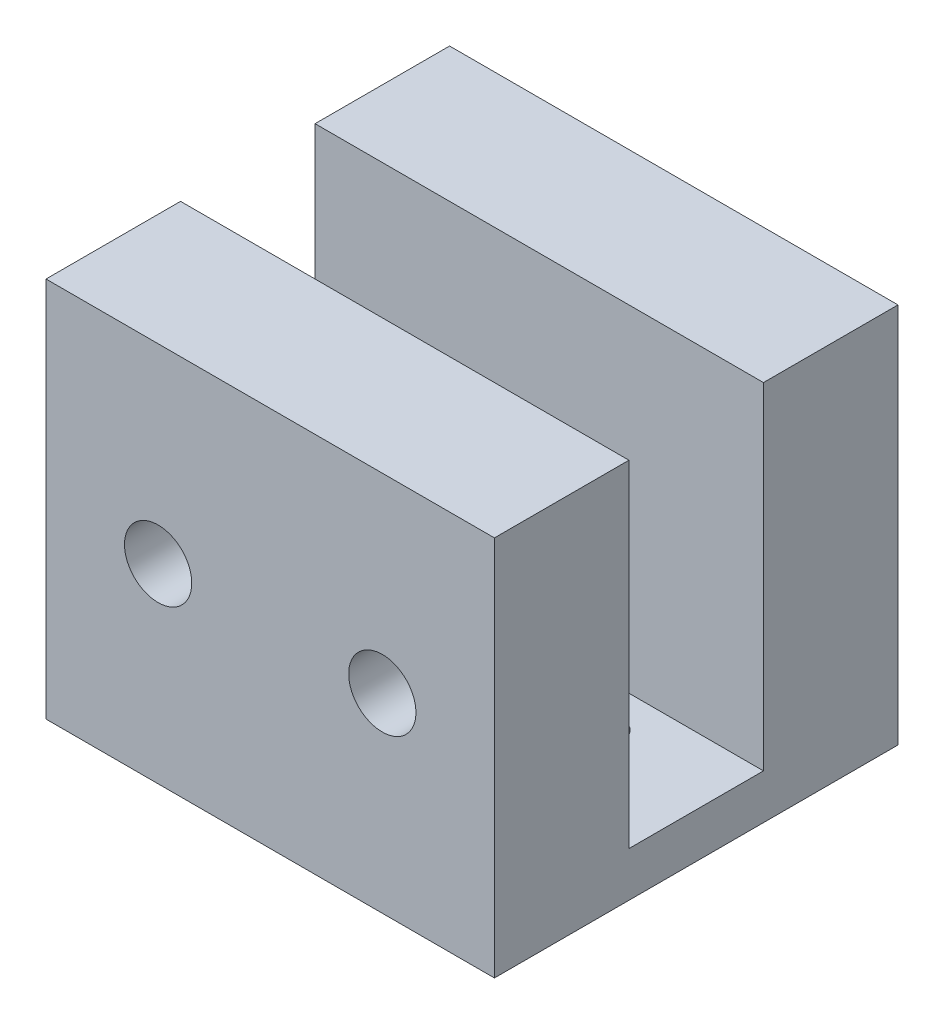
SolidWorks part; units mm, degrees
ref_plane "Plan de face" through (0, 0, 0) normal (0, 0, 1) x (1, 0, 0)
ref_plane "Plan de dessus" through (0, 0, 0) normal (0, 1, 0) x (1, 0, 0)
ref_plane "Plan de droite" through (0, 0, 0) normal (1, 0, 0) x (0, 0, -1)
sketch "Esquisse1" plane through (0, 0, 0) normal (0, 1, 0) x (1, 0, 0)
  line L0 (-10, 3) -> (10, 3)
  line L1 (-10, -9) -> (10, -9)
  line L2 (-10, -9) -> (-10, 9)
  line L3 (-10, 9) -> (10, 9)
  line L4 (10, -9) -> (10, 9)
  line L5 (-10, -9) -> (10, 9) construction
  line L6 (-10, 9) -> (10, -9) construction
  line L7 (10, 3) -> (10, -3)
  line L8 (10, -3) -> (-10, -3)
  point P0 (0, 0)
  dimension "D1" = 6
  dimension "D2" = 6
  dimension "D3" = 6
  dimension "D4" = 20
extrude "Boss.-Extru.1" add sketch "Esquisse1" along normal blind 2 contours L8 L4 L0 L2 region at (0, 0, 0)
extrude "Boss.-Extru.2" add sketch "Esquisse1<4>" along normal blind 17 contours L4 L8 L2 L1 region at (0, 0, 6)
sketch "Esquisse1<4>" plane through (0, 0, 0) normal (0, 1, 0) x (1, 0, 0) same geometry as "Esquisse1"
extrude "Boss.-Extru.3" add sketch "Esquisse1<5>" along normal blind 17 contours L0 L4 L3 L2 region at (0, 0, -6)
sketch "Esquisse1<5>" plane through (0, 0, 0) normal (0, 1, 0) x (1, 0, 0) same geometry as "Esquisse1"
sketch "Esquisse2" plane through (0, 0, 9) normal (0, 0, 1) x (1, 0, 0)
  line L0 (-10, 8.5) -> (10, 8.5) construction
  line L1 (-10, 17) -> (-10, 0) construction
  line L2 (10, 17) -> (10, 0) construction
  circle A0 centre (-5, 8.5) radius 1.5
  circle A1 centre (5, 8.5) radius 1.5
  dimension "D1" = 3
  dimension "D2" = 5
  dimension "D3" = 5
extrude "Enlèv. mat.-Extru.1" cut sketch "Esquisse2" against normal up to next
sketch "Esquisse3" plane through (0, 0, 0) normal (0, -1, 0) x (1, 0, 0)
  line L0 (4.85, -1) -> (-4.85, -1) construction
  line L4 (-10, -9) -> (10, -9) construction
  line L5 (0, 0) -> (0, -1) construction
  circle A0 centre (-4.85, -1) radius 0.85
  circle A1 centre (4.85, -1) radius 0.85
  dimension "D2" = 1.7
  dimension "D1" = 9.7
  dimension "D3" = 8
extrude "Enlèv. mat.-Extru.2" cut sketch "Esquisse3" against normal up to next
